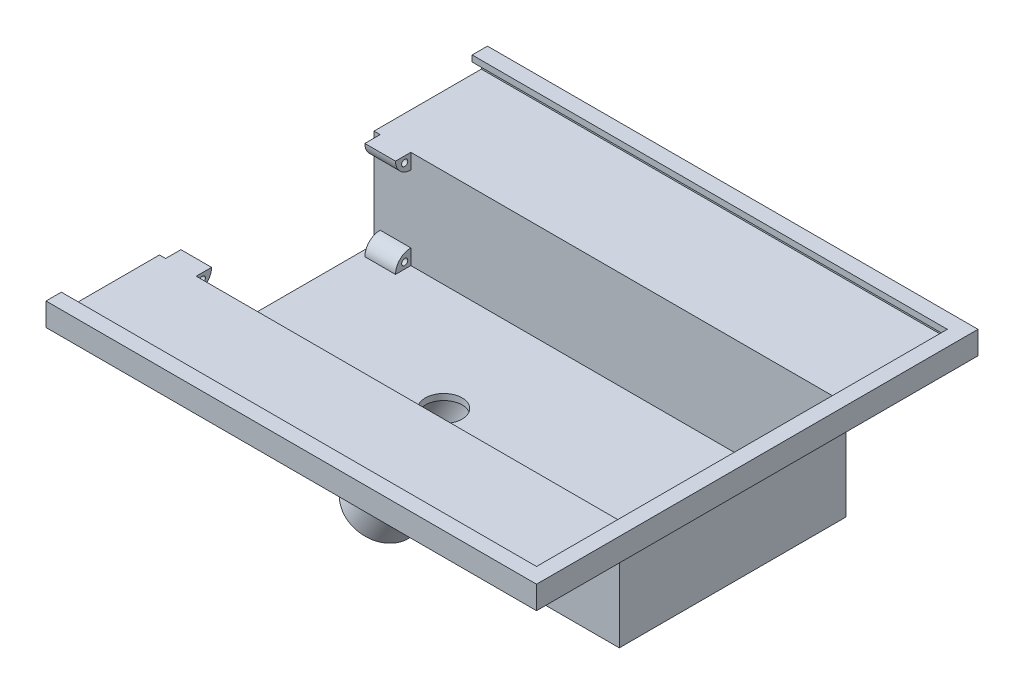
SolidWorks part; units mm, degrees
ref_plane "Plan de face" through (0, 0, 0) normal (0, 0, 1) x (1, 0, 0)
ref_plane "Plan de dessus" through (0, 0, 0) normal (0, 1, 0) x (1, 0, 0)
ref_plane "Plan de droite" through (0, 0, 0) normal (1, 0, 0) x (0, 0, -1)
sketch "Esquisse1" plane through (0, 0, 0) normal (0, 1, 0) x (1, 0, 0)
  line L0 (-150, 72) -> (-150, 35)
  line L1 (-150, 35) -> (0, 35)
  line L2 (0, 35) -> (0, -35)
  line L3 (0, -35) -> (-150, -35)
  line L4 (-150, -35) -> (-150, -72)
  line L5 (-150, -72) -> (10, -72)
  line L6 (10, -72) -> (10, 72)
  line L7 (10, 72) -> (-150, 72)
  point P2 (0, 0)
  dimension "D1" = 160
  dimension "D2" = 144
  dimension "D3" = 150
  dimension "D4" = 70
extrude "Boss.-Extru.1" add sketch "Esquisse1" along normal blind 2
sketch "Esquisse2" plane through (0, 2, 0) normal (0, 1, 0) x (1, 0, 0)
  line L0 (-150, 72) -> (10, 72)
  line L1 (10, 72) -> (10, -72)
  line L2 (10, -72) -> (-150, -72)
  line L3 (-150, -72) -> (-150, -70)
  line L4 (-150, -35) -> (-150, -72) construction
  line L5 (-150, -70) -> (8, -70)
  line L6 (8, -70) -> (8, 70)
  line L7 (8, 70) -> (-150, 70)
  line L8 (-150, 72) -> (-150, 35) construction
  line L9 (-150, 70) -> (-150, 72)
  dimension "D1" = 2
  dimension "D2" = 2
  dimension "D3" = 2
extrude "Boss.-Extru.2" add sketch "Esquisse2" along normal blind 3.5
sketch "Esquisse3" plane through (0, 5.5, 0) normal (0, 1, 0) x (1, 0, 0)
  line L1 (-150, 70) -> (-150, 35) construction
  line L2 (-150, 67) -> (5, 67)
  line L3 (5, 67) -> (5, -67)
  line L4 (5, -67) -> (-150, -67)
  line L5 (-150, -35) -> (-150, -70) construction
  line L6 (-150, -67) -> (-150, -72)
  line L7 (-150, -72) -> (10, -72)
  line L8 (10, -72) -> (10, 72)
  line L9 (10, 72) -> (-150, 72)
  line L10 (-150, 67) -> (-150, 72)
  dimension "D1" = 5
  dimension "D2" = 5
  dimension "D3" = 5
extrude "Boss.-Extru.3" add sketch "Esquisse3" along normal blind 2
sketch "Esquisse4" plane through (0, 0, 0) normal (0, -1, 0) x (1, 0, 0)
  line L0 (-150, 35) -> (0, 35)
  line L1 (0, 35) -> (0, -35)
  line L2 (0, -35) -> (-150, -35)
  line L3 (-150, -35) -> (-150, -37)
  line L4 (-150, -72) -> (-150, -35) construction
  line L5 (-150, -37) -> (2, -37)
  line L6 (2, -37) -> (2, 37)
  line L7 (2, 37) -> (-150, 37)
  line L8 (-150, 35) -> (-150, 72) construction
  line L9 (-150, 37) -> (-150, 35)
  dimension "D1" = 2
  dimension "D2" = 2
  dimension "D3" = 2
extrude "Boss.-Extru.4" add sketch "Esquisse4" along normal blind 30
sketch "Esquisse5" plane through (0, -30, 0) normal (0, -1, 0) x (1, 0, 0)
  line L1 (-150, 37) -> (2, 37)
  line L2 (-150, 37) -> (-150, -37)
  line L3 (-150, -37) -> (2, -37)
  line L4 (2, 37) -> (2, -37)
extrude "Boss.-Extru.5" add sketch "Esquisse5" along normal blind 2
sketch "Esquisse8" plane through (0, 0, 0) normal (0, 0, 1) x (1, 0, 0)
  line L0 (0, 0) -> (-47.4032, -82.1048) construction
  line L1 (0, 0) -> (-127.1616, 0) construction
  dimension "D1" = 60
sketch3d "Esquisse3D1"
  line L0 (0, 0, 0) -> (-47.4032, -82.1048, 0) construction
sketch "Esquisse9" plane through (-47.4032, -82.1048, 0) normal (0.5, 0.866, 0) x (0.866, -0.5, 0)
  line L0 (-113.9038, -37) -> (-113.9038, 37) construction
  circle A0 centre (-63.9038, 0) radius 8.25
  circle A1 centre (-63.9038, 0) radius 10.25
  dimension "D1" = 16.5
  dimension "D2" = 2
  dimension "D3" = 50
extrude "Boss.-Extru.7" add sketch "Esquisse9" along normal up to next and the other way blind 20
sketch "Esquisse10" plane through (0, -32, 0) normal (0, -1, 0) x (1, 0, 0)
  line L0 (0, 0) -> (-127.1616, 0) construction
  circle A0 centre (-92.265, 0) radius 6
  ellipse E0 centre (-92.265, 0) end of major axis (-80.4293, 0) minor radius 10.25 construction
  dimension "D1" = 12
extrude "Enlèv. mat.-Extru.2" cut sketch "Esquisse10" against normal up to next
fillet "Congé1" radius 10 1 edges at (-80.4293, -32, 0)
ref_plane "Plan1" through (-148, 0, 0) normal (-1, 0, 0) x (0, 0, 1)
sketch "Esquisse12" plane through (-148, 0, 0) normal (-1, 0, 0) x (0, 0, 1)
  line L0 (-35, 2) -> (-30, 2)
  line L1 (-70, 2) -> (70, 2) construction
  line L2 (-70, 2) -> (-35, 2) construction
  line L3 (-35, 2) -> (35, 2) construction
  line L4 (-35, 2) -> (-35, -30) construction
  line L5 (-35, -3) -> (-35, 2)
  line L6 (-35, -30) -> (-30, -30)
  line L7 (35, -30) -> (-35, -30) construction
  line L8 (-35, 2) -> (-35, -30) construction
  line L9 (-35, -25) -> (-35, -30)
  line L10 (35, -30) -> (35, -25)
  line L11 (35, 2) -> (35, -30) construction
  line L12 (30, -30) -> (35, -30)
  line L13 (35, 2) -> (35, -3)
  line L14 (35, 2) -> (35, -30) construction
  line L15 (30, 2) -> (35, 2)
  arc A0 (-30, 2) -> (-35, -3) centre (-35, 2) cw
  arc A1 (-30, -30) -> (-35, -25) centre (-35, -30) ccw
  arc A2 (35, -25) -> (30, -30) centre (35, -30) ccw
  arc A3 (35, -3) -> (30, 2) centre (35, 2) cw
  dimension "D1" = 5
extrude "Boss.-Extru.8" add sketch "Esquisse12" against normal blind 10
sketch "Esquisse13" plane through (-148, 0, 0) normal (-1, 0, 0) x (0, 0, 1)
  line L0 (-70, 2) -> (70, 2) construction
  line L1 (35, -3) -> (35, 2) construction
  line L2 (-35, 2) -> (-35, -3) construction
  line L3 (-35, -30) -> (-30, -30) construction
  circle A0 centre (33, 0) radius 1
  circle A1 centre (33, -28) radius 1
  circle A2 centre (-33, -28) radius 1
  circle A3 centre (-33, 0) radius 1
  point P12 (0, 0)
  point P13 (0, 0)
  point P14 (0, 0)
  point P15 (0, 0)
  point P20 (0, 0)
  point P21 (0, 0)
  dimension "D3" = 2
  dimension "D1" = 2
  dimension "D2" = 2
  dimension "D4" = 2
  dimension "D5" = 2
extrude "Enlèv. mat.-Extru.3" cut sketch "Esquisse13" against normal up to next
